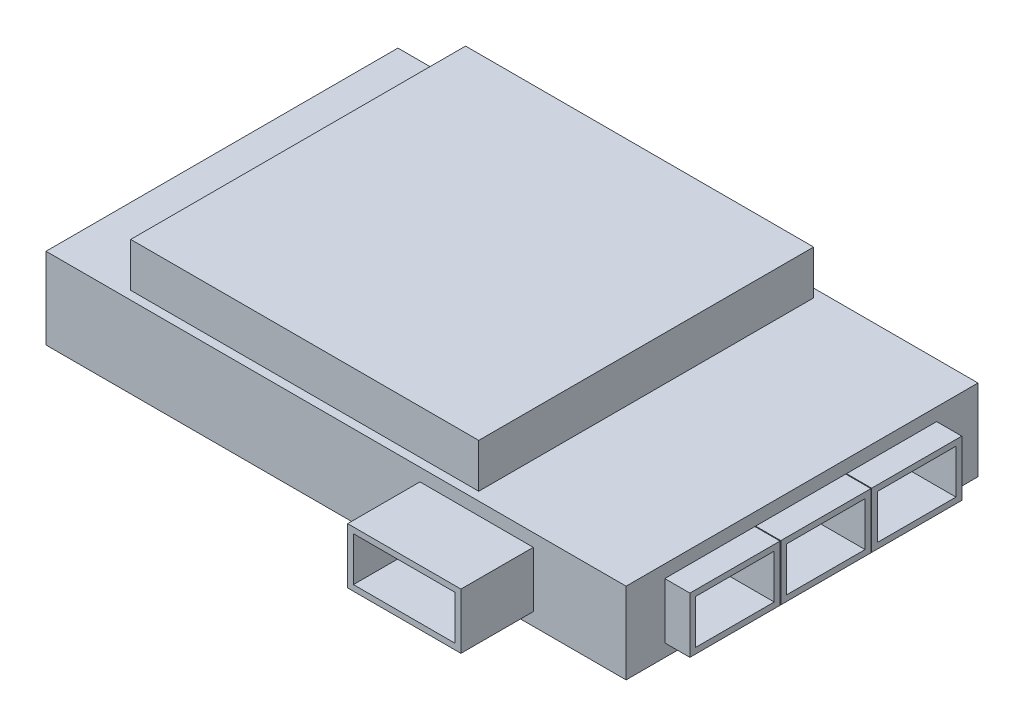
SolidWorks part; units mm, degrees
ref_plane "Front Plane" through (0, 0, 0) normal (0, 0, 1) x (1, 0, 0)
ref_plane "Top Plane" through (0, 0, 0) normal (0, 1, 0) x (1, 0, 0)
ref_plane "Right Plane" through (0, 0, 0) normal (1, 0, 0) x (0, 0, -1)
sketch "Sketch1" plane through (0, 0, 0) normal (0, 1, 0) x (1, 0, 0)
  line L1 (0, 0) -> (38.1, 0)
  line L2 (0, 0) -> (0, 23.114)
  line L3 (0, 23.114) -> (38.1, 23.114)
  line L4 (38.1, 0) -> (38.1, 23.114)
  dimension "D1" = 38.1
  dimension "D2" = 23.114
extrude "Boss-Extrude1" add sketch "Sketch1" along normal blind 5.334
sketch "Sketch2" plane through (0, 5.334, 0) normal (0, 1, 0) x (1, 0, 0)
  line L0 (0, 23.114) -> (0, 0) construction
  line L1 (5.0038, 22.5552) -> (27.8638, 22.5552)
  line L2 (5.0038, 22.5552) -> (5.0038, 0.5588)
  line L3 (5.0038, 0.5588) -> (27.8638, 0.5588)
  line L4 (27.8638, 22.5552) -> (27.8638, 0.5588)
  line L5 (10.2043, 23.114) -> (10.2043, 22.5552) construction
  line L6 (38.1, 23.114) -> (0, 23.114) construction
  line L7 (10.2043, 0.5588) -> (10.2043, 0) construction
  line L8 (0, 0) -> (38.1, 0) construction
  dimension "D1" = 22.86
  dimension "D2" = 21.9964
  dimension "D3" = 27.8638
extrude "Boss-Extrude2" add sketch "Sketch2" along normal blind 2.8956
sketch "Sketch3" plane through (0, 0, 0) normal (0, 0, 1) x (1, 0, 0)
  line L0 (27.3687, 0.8382) -> (27.3687, 0)
  line L1 (24.5618, 4.4958) -> (32.004, 4.4958)
  line L2 (24.5618, 4.4958) -> (24.5618, 0.8382)
  line L3 (24.5618, 0.8382) -> (32.004, 0.8382)
  line L4 (32.004, 4.4958) -> (32.004, 0.8382)
  line L5 (0, 0) -> (38.1, 0) construction
  line L6 (27.2439, 4.4958) -> (27.2439, 5.334)
  line L7 (5.0038, 5.334) -> (27.8638, 5.334) construction
  line L8 (38.1, 5.334) -> (38.1, 0) construction
  dimension "D1" = 7.4422
  dimension "D2" = 3.6576
  dimension "D3" = 13.5382
extrude "Boss-Extrude3" add sketch "Sketch3" along normal blind 4.7498 contours L4 L1 L2 L3 region at (28.2829, 2.667, 0)
sketch "Sketch4" plane through (0, 0, 4.7498) normal (0, 0, 1) x (1, 0, 0)
  line L0 (24.5618, 4.4958) -> (32.004, 4.4958) construction
  line L1 (24.9428, 4.1148) -> (31.623, 4.1148)
  line L2 (24.9428, 4.1148) -> (24.9428, 1.2192)
  line L3 (24.9428, 1.2192) -> (31.623, 1.2192)
  line L4 (31.623, 4.1148) -> (31.623, 1.2192)
  line L5 (28.027, 4.4958) -> (28.027, 4.1148) construction
  line L6 (28.027, 1.2192) -> (28.027, 0.8382)
  line L7 (24.5618, 0.8382) -> (32.004, 0.8382) construction
  line L8 (24.5618, 2.5653) -> (24.9428, 2.5653)
  line L9 (24.5618, 4.4958) -> (24.5618, 0.8382) construction
  line L10 (31.623, 2.5653) -> (32.004, 2.5653)
  line L11 (32.004, 4.4958) -> (32.004, 0.8382) construction
  dimension "D1" = 0.381
extrude "Cut-Extrude1" cut sketch "Sketch4" against normal blind 3.556 contours L4 L1 L2 L3 region at (28.2829, 2.667, 4.7498)
sketch "Sketch5" plane through (38.1, 0, 0) normal (1, 0, 0) x (0, 0, -1)
  line L0 (-4.7498, 4.4958) -> (-4.7498, 0.8382) construction
  line L1 (2.54, 4.4958) -> (8.4582, 4.4958)
  line L2 (2.54, 4.4958) -> (2.54, 0.8382)
  line L3 (2.54, 0.8382) -> (8.4582, 0.8382)
  line L4 (8.4582, 4.4958) -> (8.4582, 0.8382)
  line L5 (0, 5.334) -> (0, 0) construction
  line L6 (2.9148, 5.334) -> (2.9148, 4.4958) construction
  line L7 (0, 5.334) -> (23.114, 5.334) construction
  line L8 (3.0273, 0.8382) -> (3.0273, 0) construction
  line L9 (0, 0) -> (23.114, 0) construction
  dimension "D1" = 5.9182
  dimension "D2" = 8.4582
extrude "Boss-Extrude4" add sketch "Sketch5" along normal blind 1.651
sketch "Sketch6" plane through (39.751, 0, 0) normal (1, 0, 0) x (0, 0, -1)
  line L0 (3.2654, 4.4958) -> (3.2654, 4.1148) construction
  line L1 (2.921, 4.1148) -> (8.0772, 4.1148)
  line L2 (2.921, 4.1148) -> (2.921, 1.2192)
  line L3 (2.921, 1.2192) -> (8.0772, 1.2192)
  line L4 (8.0772, 4.1148) -> (8.0772, 1.2192)
  line L5 (8.4582, 4.4958) -> (2.54, 4.4958) construction
  line L7 (3.2654, 1.2192) -> (3.2654, 0.8382) construction
  line L8 (2.54, 0.8382) -> (8.4582, 0.8382) construction
  line L9 (2.54, 3.2148) -> (2.921, 3.2148) construction
  line L10 (2.54, 4.4958) -> (2.54, 0.8382) construction
  line L12 (8.0772, 3.2148) -> (8.4582, 3.2148) construction
  line L13 (8.4582, 0.8382) -> (8.4582, 4.4958) construction
  dimension "D1" = 0.381
extrude "Cut-Extrude2" cut sketch "Sketch6" against normal blind 3.3782
pattern_linear "LPattern1" count 3 spacing 5.969 along (0, 0, -1) of "Boss-Extrude4", "Cut-Extrude2"
